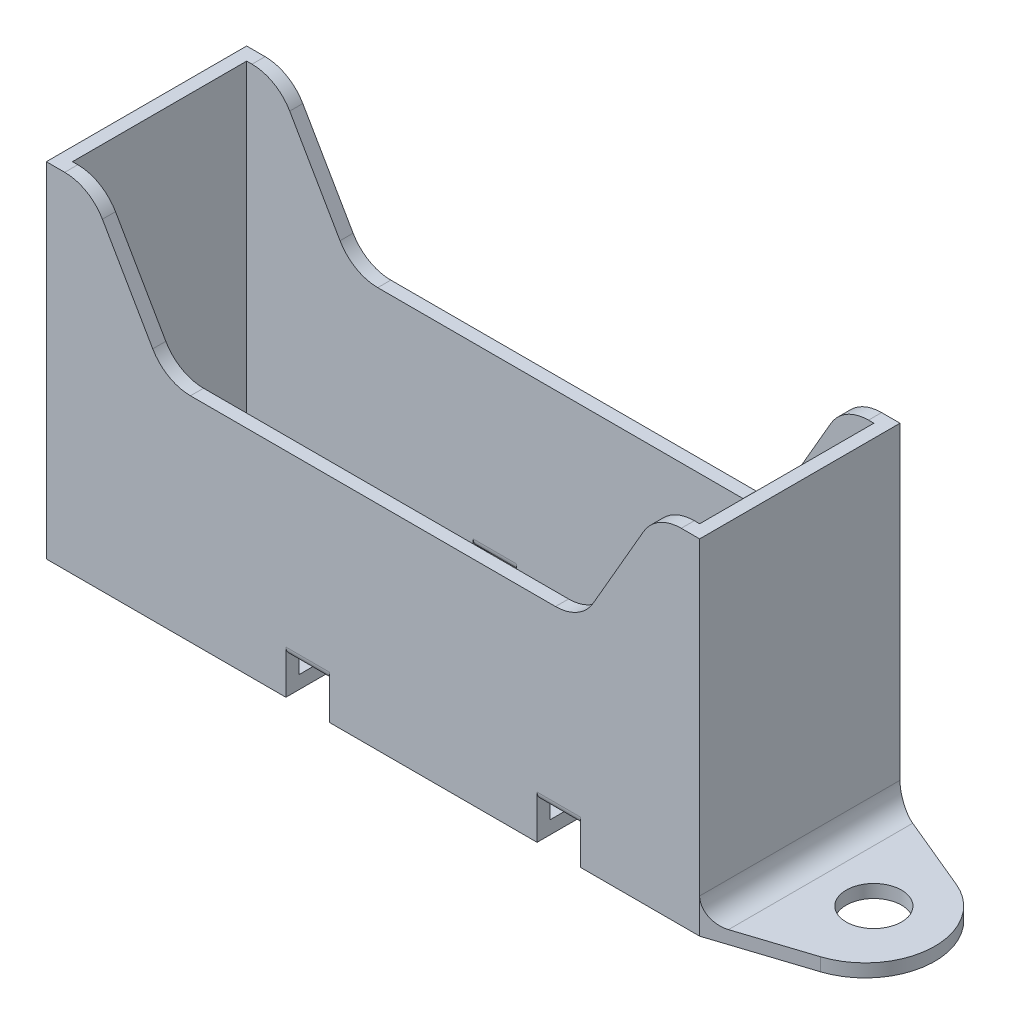
SolidWorks part; units mm, degrees
ref_plane "Front Plane" through (0, 0, 0) normal (0, 0, 1) x (1, 0, 0)
ref_plane "Top Plane" through (0, 0, 0) normal (0, 1, 0) x (1, 0, 0)
ref_plane "Right Plane" through (0, 0, 0) normal (1, 0, 0) x (0, 0, -1)
sketch "Sketch15" plane through (0, 0, 0) normal (0, 1, 0) x (1, 0, 0)
  line L0 (-37.5, -11.5) -> (-37.5, 11.5)
  line L1 (-36, -10) -> (36, -10)
  line L2 (-36, -10) -> (-36, 10)
  line L3 (-36, 10) -> (36, 10)
  line L4 (36, -10) -> (36, 10)
  line L5 (-36, -10) -> (36, 10) construction
  line L6 (-36, 10) -> (36, -10) construction
  line L7 (-37.5, 11.5) -> (37.5, 11.5)
  line L8 (37.5, -11.5) -> (37.5, 11.5)
  line L9 (-37.5, -11.5) -> (37.5, -11.5)
  point P0 (0, 0)
  dimension "D1" = 72
  dimension "D2" = 20
  dimension "D3" = 1.5
extrude "Boss-Extrude8" add sketch "Sketch15" along normal blind 38
sketch "Sketch18" plane through (0, 0, 0) normal (0, -1, 0) x (1, 0, 0)
  line L0 (-37.5, 11.5) -> (37.5, 11.5)
  line L1 (37.5, 11.5) -> (47.9649, 8.1108)
  line L2 (48.5769, -6.8846) -> (37.5, -11.5)
  line L3 (37.5, 11.5) -> (37.5, -11.5) construction
  line L4 (37.5, -11.5) -> (-11.3457, -11.5)
  line L8 (-37.5, 11.5) -> (-37.5, -11.5)
  line L10 (-23.1374, -19) -> (-23.1374, -27) construction
  line L12 (-11.3457, -11.5) -> (-15.7528, -22.0769)
  line L13 (-34.9291, -11.5) -> (-30.522, -22.0769)
  line L14 (-34.9291, -11.5) -> (-37.5, -11.5)
  arc A0 (47.9649, 8.1108) -> (48.5769, -6.8846) centre (45.5, 0.5) cw
  arc A3 (-15.7528, -22.0769) -> (-30.522, -22.0769) centre (-23.1374, -19) cw
  circle A4 centre (-23.1374, -19) radius 3 construction
  circle A5 centre (-23.1374, -19) radius 3 construction
  point P7 (-9.2778, -17.6293)
  dimension "D1" = 8
  dimension "D8" = 8
  dimension "D2" = 8
  dimension "D3" = 67.38
  dimension "D10" = 67.38
extrude "Boss-Extrude11" add sketch "Sketch18" along normal blind 1.5
hole_wizard "1/4 (0.25) Diameter Hole1" positions "Sketch19" profile "Sketch20" hole size "1/4" standard "ANSI Inch" end condition through all
sketch "Sketch19" plane through (0, 0, 0) normal (0, 1, 0) x (1, 0, 0)
  point P8 (46, 0)
  point P10 (46, 0)
  point P21 (-23.1374, 19)
sketch "Sketch20" plane through (46, 0, 0) normal (1, 0, 0) x (0, 0, 1)
  line L0 (0, 0) -> (0, 1.5)
  line L1 (0, 1.5) -> (3.175, 1.5)
  line L2 (3.175, 1.5) -> (3.175, 0)
  line L5 (3.175, 0) -> (0, 0)
  line L11 (0, -6.35) -> (0, 107.95) construction
  dimension "Thru Hole Dia." = 6.35
  dimension "Thru Hole Depth" = 1.5
sketch "Sketch21" plane through (0, 0, -11.5) normal (0, 0, -1) x (-1, 0, 0)
  line L0 (0, -4.7141) -> (0, 50.0572) construction
  line L1 (-32.5, 38) -> (-23.8397, 23)
  line L2 (-37.5, 38) -> (37.5, 38) construction
  line L3 (-23.8397, 23) -> (23.8397, 23)
  line L4 (23.8397, 23) -> (32.5, 38)
  line L5 (32.5, 38) -> (-32.5, 38)
  line L6 (11.3457, -1.5) -> (-37.5, -1.5) construction
  line L7 (-23.8397, -1.5) -> (-18.8397, -1.5)
  line L8 (-23.8397, -1.5) -> (-23.8397, 2.5)
  line L9 (-23.8397, 2.5) -> (-18.8397, 2.5)
  line L10 (-18.8397, -1.5) -> (-18.8397, 2.5)
  line L12 (5, -1.5) -> (10, -1.5)
  line L13 (5, -1.5) -> (5, 2.5)
  line L14 (5, 2.5) -> (10, 2.5)
  line L15 (10, -1.5) -> (10, 2.5)
  dimension "D1" = 60
  dimension "D2" = 5
  dimension "D3" = 15
  dimension "D4" = 5
  dimension "D5" = 5
  dimension "D6" = 5
  dimension "D7" = 4
extrude "Cut-Extrude1" cut sketch "Sketch21" against normal through all
fillet "Fillet1" radius 5 8 edges at (-32.5, 38, 10.75) (32.5, 38, 10.75) (-32.5, 38, -10.75) (-23.8397, 23, -10.75) (-23.8397, 23, 10.75) (23.8397, 23, 10.75) (32.5, 38, -10.75) (23.8397, 23, -10.75)
fillet "Fillet2" radius 1 8 edges at (21.3397, 2.5, -11.5) (21.3397, 2.5, -10) (21.3397, 2.5, 10) (21.3397, 2.5, 11.5) (-7.5, 2.5, -11.5) (-7.5, 2.5, -10) (-7.5, 2.5, 10) (-7.5, 2.5, 11.5)
fillet "Fillet3" radius 2.5 2 edges at (37.5, 0, 0) (-23.1374, 0, -11.5)
